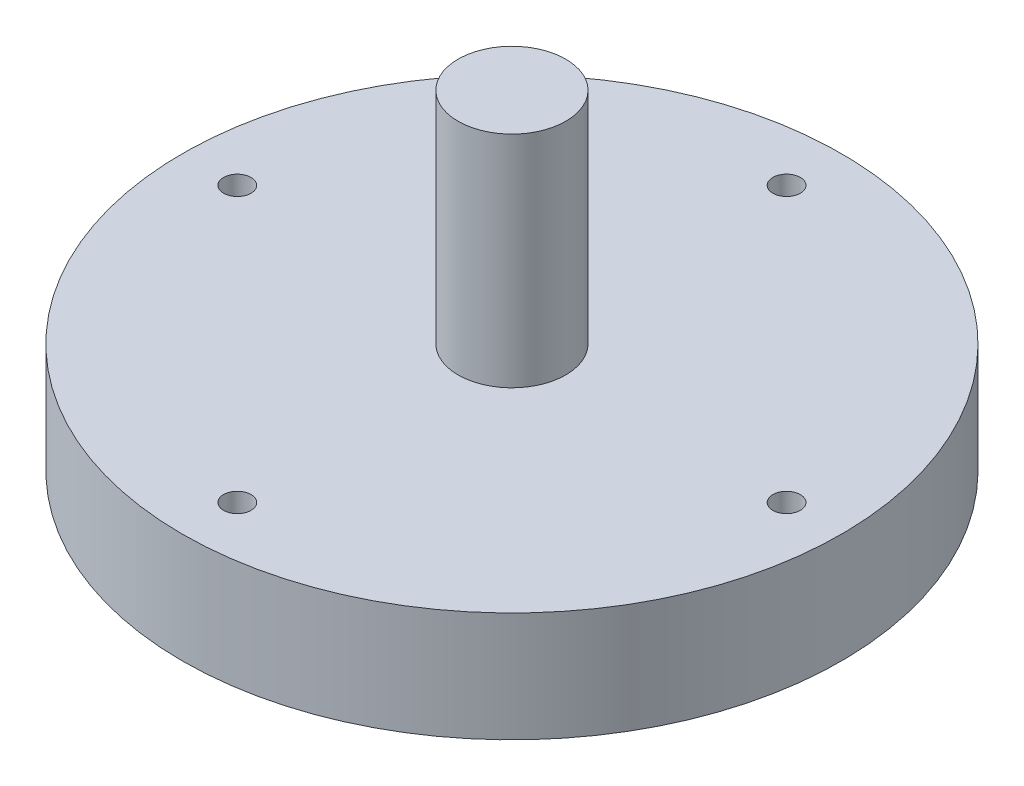
SolidWorks part; units mm, degrees
ref_plane "Front Plane" through (0, 0, 0) normal (0, 0, 1) x (1, 0, 0)
ref_plane "Top Plane" through (0, 0, 0) normal (0, 1, 0) x (1, 0, 0)
ref_plane "Right Plane" through (0, 0, 0) normal (1, 0, 0) x (0, 0, -1)
sketch "Sketch1" plane through (0, 0, 0) normal (0, 1, 0) x (1, 0, 0)
  circle A0 centre (0, 0) radius 38.1
  dimension "D1" = 76.2
extrude "Boss-Extrude1" add sketch "Sketch1" along normal blind 12.7
sketch "Sketch2" plane through (0, 12.7, 0) normal (0, 1, 0) x (1, 0, 0)
  circle A0 centre (0, 0) radius 6.223
  dimension "D1" = 12.446
extrude "Boss-Extrude2" add sketch "Sketch2" along normal blind 25.4
sketch "Sketch3" plane through (0, 12.7, 0) normal (0, 1, 0) x (1, 0, 0)
  line L0 (0, 31.75) -> (0, 0) construction
  circle A0 centre (0, 31.75) radius 1.5875
  dimension "D1" = 3.175
  dimension "D2" = 31.75
extrude "Cut-Extrude1" cut sketch "Sketch3" against normal through all
pattern_circular "CirPattern1" count 4 over 360 about axis through (0, 12.7, 0) along (0, 1, 0) of "Cut-Extrude1"
